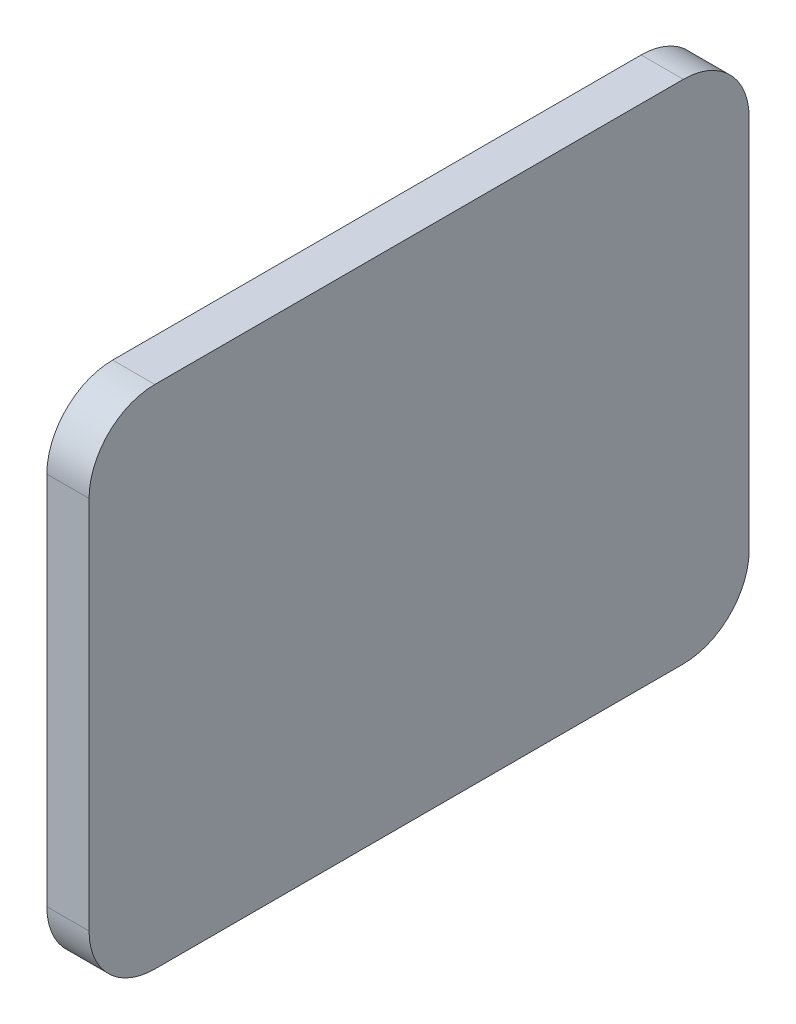
SolidWorks part; units mm, degrees
ref_plane "Front Plane" through (0, 0, 0) normal (0, 0, 1) x (1, 0, 0)
ref_plane "Top Plane" through (0, 0, 0) normal (0, 1, 0) x (1, 0, 0)
ref_plane "Right Plane" through (0, 0, 0) normal (1, 0, 0) x (0, 0, -1)
ref_plane "Plane1" through (38.1, 0, 0) normal (-1, 0, 0) x (0, 0, 1)
sketch "Sketch1" plane through (38.1, 0, 0) normal (-1, 0, 0) x (0, 0, 1)
  line L0 (152.4, 15.5575) -> (0, 15.5575) construction
  line L1 (0, -15.5575) -> (152.4, -15.5575) construction
  line L6 (9.0952, 15.24) -> (40.911, 15.24)
  line L7 (44.8734, 11.2776) -> (44.8734, -11.2776)
  line L8 (40.911, -15.24) -> (9.0952, -15.24)
  line L9 (5.1328, -11.2776) -> (5.1328, 11.2776)
  circle A0 centre (9.0952, 11.2776) radius 2.6924 construction
  circle A1 centre (40.911, 11.2776) radius 2.6924 construction
  circle A2 centre (40.911, -11.2776) radius 2.6924 construction
  circle A3 centre (9.0952, -11.2776) radius 2.6924 construction
  circle A4 centre (9.0952, 11.2776) radius 4.2799 construction
  circle A5 centre (40.911, 11.2776) radius 4.2799 construction
  circle A6 centre (40.911, -11.2776) radius 4.2799 construction
  circle A7 centre (9.0952, -11.2776) radius 4.2799 construction
  circle A8 centre (9.0952, 11.2776) radius 1.4224 construction
  circle A9 centre (25.0031, 0) radius 15.22 construction
  arc A10 (40.911, 15.24) -> (44.8734, 11.2776) centre (40.911, 11.2776) cw
  arc A11 (44.8734, -11.2776) -> (40.911, -15.24) centre (40.911, -11.2776) cw
  arc A12 (9.0952, -15.24) -> (5.1328, -11.2776) centre (9.0952, -11.2776) cw
  arc A13 (5.1328, 11.2776) -> (9.0952, 15.24) centre (9.0952, 11.2776) cw
  dimension "D1" = 5.3848
  dimension "D2" = 1.5875
  dimension "D3" = 2.8448
  dimension "D4" = 1.27
extrude "Boss-Extrude1" add sketch "Sketch1" along normal blind 2.54
